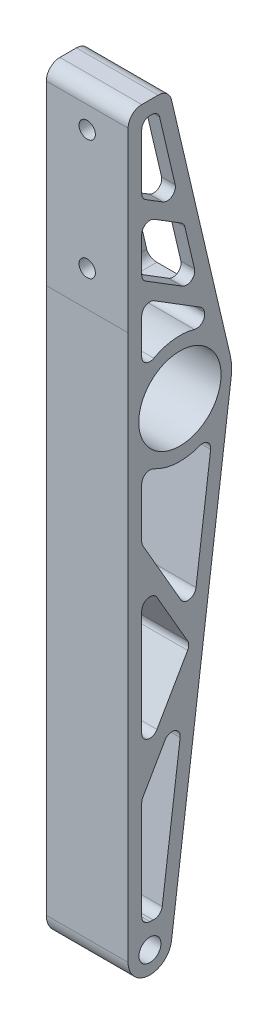
SolidWorks part; units mm, degrees
material "6061-T6 (SS)"
ref_plane "Front Plane" through (0, 0, 0) normal (0, 0, 1) x (1, 0, 0)
ref_plane "Top Plane" through (0, 0, 0) normal (0, 1, 0) x (1, 0, 0)
ref_plane "Right Plane" through (0, 0, 0) normal (1, 0, 0) x (0, 0, -1)
sketch "Sketch1" plane through (0, 0, 0) normal (1, 0, 0) x (0, 0, -1)
  line L0 (-8, 0) -> (-8, 270)
  line L1 (11, 169.6437) -> (0, 0) construction
  line L2 (7.933, -1.0331) -> (29.8409, 167.1901)
  line L3 (-8, 270) -> (7, 270)
  line L4 (7, 270) -> (29.499, 173.9783)
  circle A0 centre (0, 0) radius 4.05
  arc A1 (-8, 0) -> (7.933, -1.0331) centre (0, 0) ccw
  arc A2 (29.8409, 167.1901) -> (29.499, 173.9783) centre (11, 169.6437) ccw
  circle A3 centre (11, 169.6437) radius 15.1
  dimension "D1" = 8.1
  dimension "D2" = 16
  dimension "D4" = 38
  dimension "D6" = 30.2
  dimension "D3" = 270
  dimension "D5" = 170
  dimension "D7" = 15
extrude "Boss-Extrude1" add sketch "Sketch1" along normal blind 15 and the other way blind 15
sketch "Sketch3" plane through (0, 0, 8) normal (0, 0, 1) x (1, 0, 0)
  line L0 (15, 270) -> (15, 0) construction
  line L1 (-15, 270) -> (15, 270)
  line L2 (-15, 270) -> (-15, 200)
  line L3 (-15, 200) -> (15, 200)
  line L4 (15, 270) -> (15, 200)
  dimension "D1" = 70
split line "Split Line1"
sketch "Sketch5" plane through (0, 0, 0) normal (1, 0, 0) x (0, 0, -1)
  line L1 (-3, 265) -> (63.8342, 265)
  line L2 (-3, 265) -> (-3, 195.1437)
  line L3 (-3, 195.1437) -> (63.8342, 195.1437)
  line L4 (63.8342, 265) -> (63.8342, 195.1437)
  line L5 (-8, 270) -> (-8, 200) construction
  line L6 (7, 270) -> (-8, 270) construction
  circle A0 centre (11, 169.6437) radius 15.1 construction
  point P4 (-3, 256.1468)
  dimension "D1" = 5
  dimension "D2" = 25.5
  dimension "D3" = 5
extrude "Cut-Extrude2" cut sketch "Sketch5" against normal blind 10 and the other way blind 10
sketch "Sketch4" plane through (15, 0, 0) normal (1, 0, 0) x (0, 0, -1)
  line L0 (-3, 155.3609) -> (-3, 8.4853)
  line L1 (-8, 200) -> (-8, 0) construction
  line L2 (23.0383, 153.6725) -> (4.0707, 8.0268)
  line L3 (7.933, -1.0331) -> (29.8409, 167.1901) construction
  line L4 (-3, 183.9266) -> (-3, 265)
  line L5 (-3, 265) -> (3.0361, 265)
  line L6 (3.0361, 265) -> (21.3724, 186.7438)
  line L7 (-3, 240) -> (10.9167, 231.3669)
  line L8 (29.499, 173.9783) -> (7, 270) construction
  line L9 (7, 270) -> (-8, 270) construction
  line L10 (-3, 130.3609) -> (15.7688, 97.8524)
  line L11 (-3, 120.3609) -> (14.7061, 89.6929)
  line L12 (-3, 234.1161) -> (12.5299, 224.4823)
  line L13 (-3, 214.1161) -> (18.0131, 201.0809)
  line L14 (14.7061, 89.6929) -> (-3, 59.025)
  line L15 (13.0245, 76.7803) -> (-3, 49.025)
  line L16 (-3, 208.2322) -> (19.6262, 194.1963)
  circle A0 centre (0, 0) radius 9
  circle A1 centre (11, 169.6437) radius 20
  dimension "D1" = 40
  dimension "D2" = 18
  dimension "D3" = 5
  dimension "D4" = 5
  dimension "D5" = 5
  dimension "D6" = 5
  dimension "D7" = 5
  dimension "D8" = 45
  dimension "D9" = 25
  dimension "D10" = 25
  dimension "D11" = 30
  dimension "D12" = 30
  dimension "D13" = 5
  dimension "D14" = 5
  dimension "D15" = 45
  dimension "D16" = 20
  dimension "D17" = 5
extrude "Cut-Extrude1" cut sketch "Sketch4" against normal through all both and the other way through all contours A1 L0 L10 L2 | A0 L2 L11 L0 | A1 L6 L4 | L4 L6 L5 | L14 L11 L0 | L4 L13 L6 L12 region at (15, 131.8968, -9.8249) region at (15, 195.1997, -6.0352) region at (15, 89.6929, -2.902) region at (15, 217.9062, -6.2043) region at (15, 39.0713, -3.3723) region at (15, 248.5264, -2.3803)
fillet "Fillet1" radius 3 35 edges at (0, 186.7438, -21.3724) (0, 183.9266, 3) (0, 194.1963, -19.6262) (-12.5, 208.2322, 3) (12.5, 224.4823, -12.5299) (-12.5, 224.4823, -12.5299) (12.5, 201.0809, -18.0131) (-12.5, 214.1161, 3) (12.5, 214.1161, 3) (12.5, 208.2322, 3) (-12.5, 234.1161, 3) (12.5, 234.1161, 3) (12.5, 231.3669, -10.9167) (-12.5, 231.3669, -10.9167) (12.5, 265, -3.0361) (-12.5, 265, -3.0361) (-12.5, 240, 3) (12.5, 240, 3) (0, 265, 3) (0, 8.0268, -4.0707) (0, 8.4853, 3) (0, 49.025, 3) (0, 76.7803, -13.0245) (0, 59.025, 3) (0, 89.6929, -14.7061) (0, 120.3609, 3) (0, 97.8524, -15.7688) (0, 130.3609, 3) (0, 153.6725, -23.0383) (0, 155.3609, 3) (-12.5, 201.0809, -18.0131) (-10, 265, -5.6038) (10, 265, -5.6038) (-10, 195.1437, -21.3193) (10, 195.1437, -21.3193)
fillet "Fillet2" radius 5 2 edges at (0, 270, 8) (0, 270, -7)
sketch "Sketch6" plane through (0, 0, 8) normal (0, 0, 1) x (1, 0, 0)
  circle A0 centre (0, 257) radius 3
  circle A1 centre (0, 213) radius 3
extrude "Cut-Extrude3" cut sketch "Sketch6" against normal blind 5
